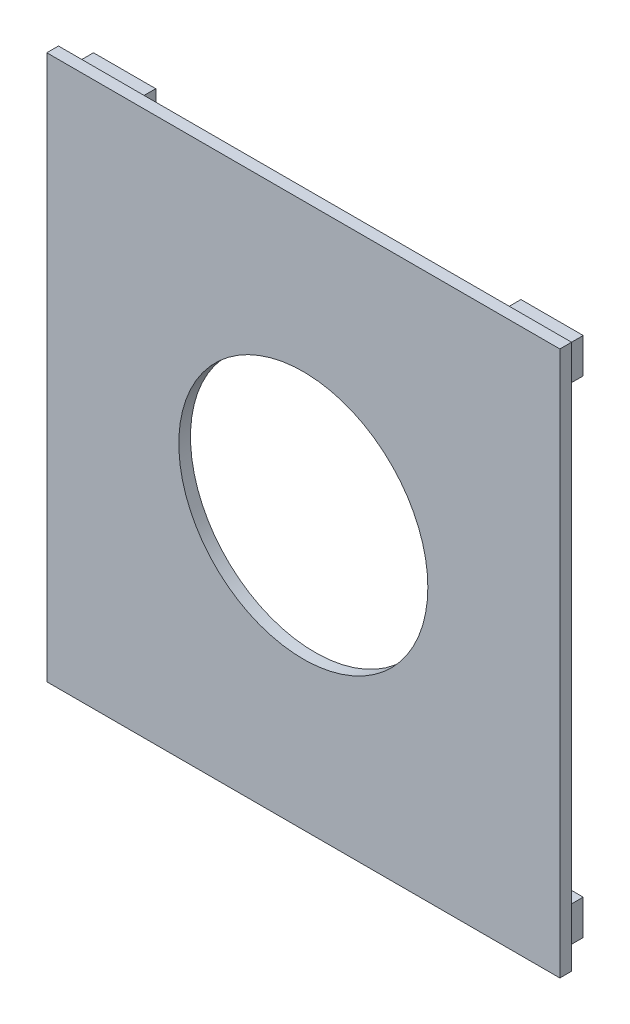
SolidWorks part; units mm, degrees
ref_plane "Front Plane" through (0, 0, 0) normal (0, 0, 1) x (1, 0, 0)
ref_plane "Top Plane" through (0, 0, 0) normal (0, 1, 0) x (1, 0, 0)
ref_plane "Right Plane" through (0, 0, 0) normal (1, 0, 0) x (0, 0, -1)
sketch "Sketch1" plane through (0, 0, 0) normal (0, 0, 1) x (1, 0, 0)
  line L0 (-10.75, -9.75) -> (121.1, -9.75) construction
  line L2 (121.1, -9.75) -> (55.175, -9.75)
  line L3 (121.1, -9.75) -> (121.1, 60.25)
  line L4 (121.1, 60.25) -> (55.175, 60.25)
  line L5 (55.175, -9.75) -> (55.175, 60.25)
  line L6 (-10.75, -9.75) -> (-10.75, 15.25) construction
  line L7 (-10.75, -9.75) -> (-10.75, 15.25) construction
  point P8 (55.175, -9.75)
extrude "Boss-Extrude1" add sketch "Sketch1" along normal blind 1.5 contours L5 L2 L3 L4
sketch "Sketch2" plane through (0, 0, 1.5) normal (0, 0, 1) x (1, 0, 0)
  line L4 (93.6475, 22.3) -> (93.7375, 22.3)
  line L5 (93.7375, 28.2) -> (93.6475, 28.2)
  line L6 (93.6475, 22.3) -> (93.7375, 22.3)
  line L7 (93.7375, 28.2) -> (93.6475, 28.2)
  arc A8 (93.7375, 22.3) -> (93.7375, 28.2) centre (93.7375, 25.25) ccw
  arc A9 (93.6475, 28.2) -> (93.6475, 22.3) centre (88.1375, 25.25) ccw
  arc A10 (93.7375, 22.3) -> (93.7375, 28.2) centre (93.7375, 25.25) ccw
  arc A11 (93.6475, 28.2) -> (93.6475, 22.3) centre (88.1375, 25.25) ccw
  dimension "D1" = 0.25
ref_plane "Plane2" through (88.1375, 0, 0) normal (1, 0, 0) x (0, 0, -1)
ref_plane "Plane1" through (0, 25.25, 0) normal (0, 1, 0) x (1, 0, 0)
sketch "Sketch4" plane through (0, 0, 0) normal (0, 0, -1) x (-1, 0, 0)
  line L0 (-118.1, 57.25) -> (-118.1, 55.75)
  line L1 (-119.6, 58.75) -> (-111.6, 58.75)
  line L2 (-119.6, 58.75) -> (-119.6, 54.25)
  line L3 (-119.6, 54.25) -> (-111.6, 54.25)
  line L4 (-111.6, 58.75) -> (-111.6, 54.25)
  line L5 (-119.6, 58.75) -> (-119.6, 60.25) construction
  line L6 (-118.1, 55.75) -> (-113.1, 55.75)
  line L8 (-113.1, 57.25) -> (-113.1, 55.75)
  line L9 (-118.1, 57.25) -> (-113.1, 57.25)
  line L10 (-119.6, 58.75) -> (-121.1, 58.75) construction
  line L12 (-121.1, 60.25) -> (-55.175, 60.25) construction
  line L13 (-121.1, -9.75) -> (-121.1, 60.25) construction
  dimension "D1" = 1.5
  dimension "D2" = 5
  dimension "D3" = 1.5
extrude "Boss-Extrude2" add sketch "Sketch4" along normal blind 3
mirror "Mirror1" about plane through (88.1375, 0, 0) normal (1, 0, 0) of "Boss-Extrude2"
mirror "Mirror2" about plane through (0, 25.25, 0) normal (0, 1, 0) of "Mirror1", "Boss-Extrude2"
sketch "Sketch3" [suppressed] plane through (121.1, 0, 0) normal (1, 0, 0) x (0, 0, -1)
  line L0 (0, -9.75) -> (0, 60.25) construction
  line L1 (-1.5, 60.25) -> (6, 60.25)
  line L2 (-1.5, 60.25) -> (-1.5, 61.75)
  line L3 (-1.5, 61.75) -> (6, 61.75)
  line L4 (6, 60.25) -> (6, 61.75)
  line L5 (6, 60.25) -> (4.5, 58.75)
  line L7 (4.5, 58.75) -> (4.5, 60.25)
  dimension "D1" = 1.5
  dimension "D2" = 6
  dimension "D3" = 45
sketch "Sketch5" plane through (0, 0, 1.5) normal (0, 0, 1) x (1, 0, 0)
  circle A0 centre (88.1375, 25.25) radius 16
extrude "Cut-Extrude1" cut sketch "Sketch5" against normal up to next
equation "\"D1@Boss-Extrude2\"=1.50mm+.25"
